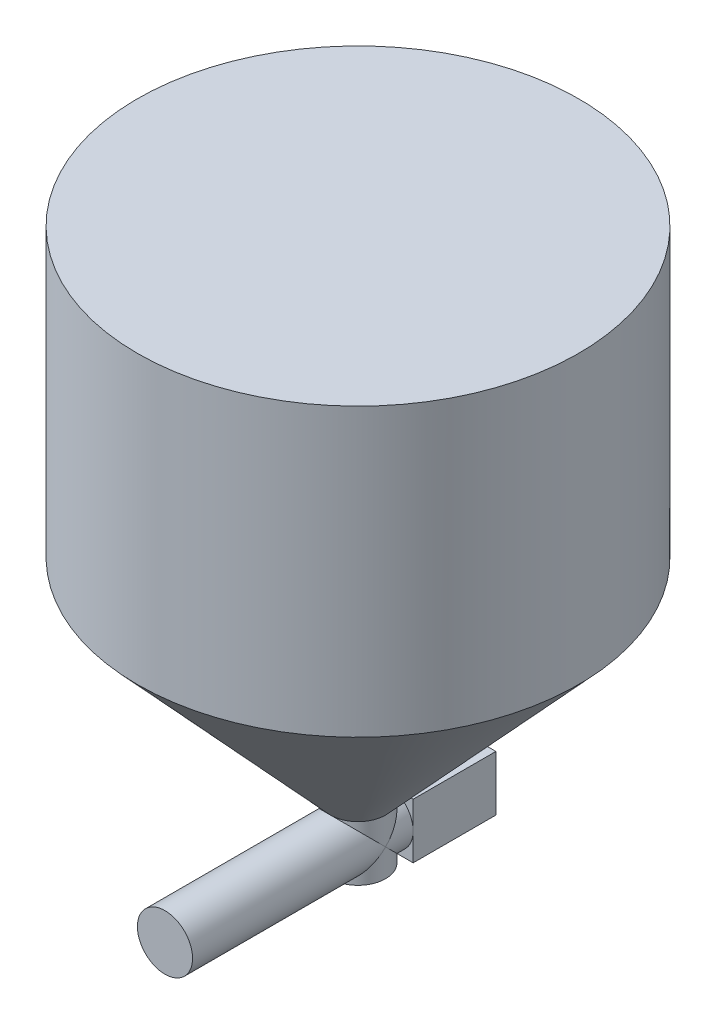
SolidWorks part; units mm, degrees
ref_plane "Alzado" through (0, 0, 0) normal (0, 0, 1) x (1, 0, 0)
ref_plane "Planta" through (0, 0, 0) normal (0, 1, 0) x (1, 0, 0)
ref_plane "Vista lateral" through (0, 0, 0) normal (1, 0, 0) x (0, 0, -1)
sketch "Croquis1" plane through (0, 0, 0) normal (0, 1, 0) x (1, 0, 0)
  circle A0 centre (0, 0) radius 400
  dimension "D1" = 800
ref_plane "Plano1" through (0, -900, 0) normal (0, 1, 0) x (1, 0, 0)
extrude "Saliente-Extruir1" add sketch "Croquis1" against normal blind 520 contours A0
sketch "Croquis2" plane through (0, -520, 0) normal (0, -1, 0) x (1, 0, 0)
  circle A0 centre (0, 0) radius 400
  dimension "D1" = 800
sketch "Croquis3" plane through (0, -900, 0) normal (0, 1, 0) x (1, 0, 0)
  circle A0 centre (0, 0) radius 50
  dimension "D1" = 100
loft "Recubrir1" add profiles "Croquis3", "Croquis2" connector at (-49.9253, -900, 2.7318) connector at (-399.2107, -520, 25.1162)
sketch "Croquis4" plane through (0, -900, 0) normal (0, -1, 0) x (1, 0, 0)
  circle A0 centre (0, 0) radius 50
extrude "Saliente-Extruir2" add sketch "Croquis4" along normal blind 100
ref_plane "Plano2" through (0, 0, -50) normal (0, 0, -1) x (-1, 0, 0)
sketch "Croquis5" plane through (0, 0, -50) normal (0, 0, -1) x (-1, 0, 0)
  line L0 (-50, -1000) -> (50, -1000) construction
  line L3 (0, -1000) -> (0, -900) construction
  line L4 (440, -900) -> (-440, -900) construction
  circle A0 centre (0, -950) radius 50
extrude "Saliente-Extruir3" add sketch "Croquis5" against normal blind 400
sketch "Croquis6" plane through (0, 0, -50) normal (0, 0, -1) x (-1, 0, 0)
  line L0 (50, -950) -> (-50, -950) construction
  line L2 (-50, -900) -> (50, -900)
  line L3 (-50, -900) -> (-50, -1000)
  line L4 (-50, -1000) -> (50, -1000)
  line L5 (50, -900) -> (50, -1000)
  line L6 (-50, -900) -> (50, -1000) construction
  line L7 (-50, -1000) -> (50, -900) construction
  circle A0 centre (0, -950) radius 50 construction
  circle A1 centre (0, -950) radius 50 construction
  point P8 (0, -950)
  dimension "D1" = 100
  dimension "D2" = 100
  dimension "D3" = 50
extrude "Saliente-Extruir4" add sketch "Croquis6" along normal blind 150
